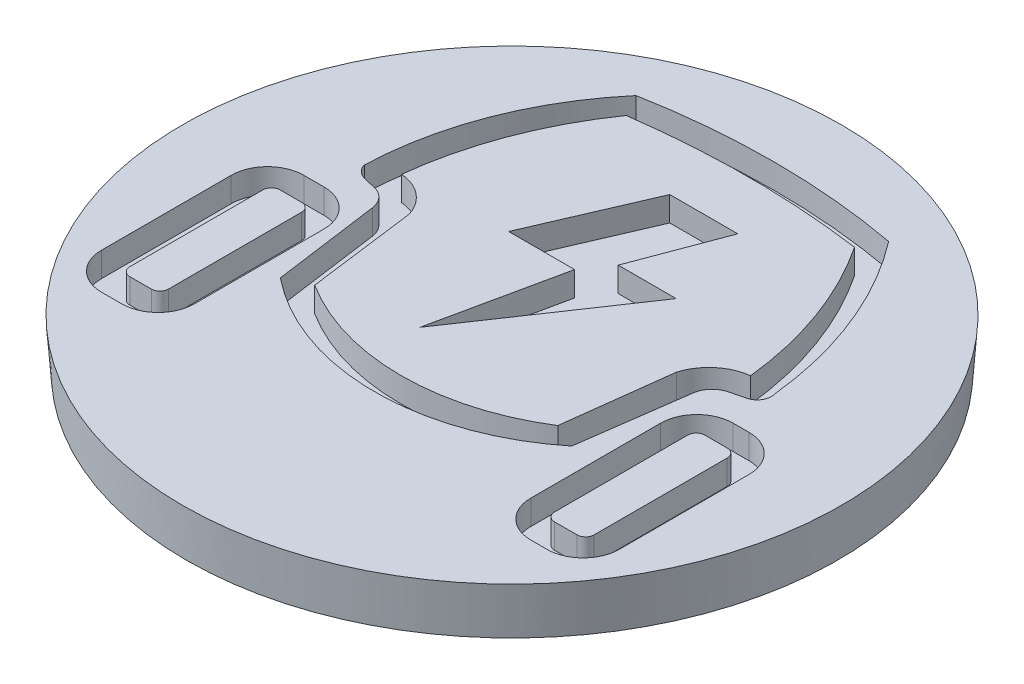
SolidWorks part; units mm, degrees
ref_plane "Alzado" through (0, 0, 0) normal (0, 0, 1) x (1, 0, 0)
ref_plane "Planta" through (0, 0, 0) normal (0, 1, 0) x (1, 0, 0)
ref_plane "Vista lateral" through (0, 0, 0) normal (1, 0, 0) x (0, 0, -1)
sketch "Croquis1" plane through (0, 0, 0) normal (0, 1, 0) x (1, 0, 0)
  circle A0 centre (0, 0) radius 26.25
extrude "Saliente-Extruir1" add sketch "Croquis1" along normal blind 4
sketch "Croquis2" plane through (0, 4, 0) normal (0, 1, 0) x (1, 0, 0)
  line L0 (48.0381, 307.552) -> (528.0381, 307.552) construction
  line L1 (-2.8746, -4.5969) -> (5.5025, 7.8219)
  line L2 (-18.2132, -0.6112) -> (-16.4707, -0.6112)
  line L3 (-18.9132, -1.3112) -> (-18.9132, -12.1089)
  line L4 (-18.2132, -12.8089) -> (-16.4707, -12.8089)
  line L5 (-15.7707, -1.3112) -> (-15.7707, -12.1089)
  line L6 (-18.2718, 1.3787) -> (-16.6299, 1.3787)
  line L7 (-21.2218, -1.5713) -> (-21.2218, -12.0991)
  line L8 (-18.2718, -15.0491) -> (-16.6299, -15.0491)
  line L9 (-13.6799, -1.5713) -> (-13.6799, -12.0991)
  line L10 (16.2668, -0.6112) -> (18.0817, -0.6112)
  line L11 (15.5668, -1.3112) -> (15.5668, -12.1089)
  line L12 (16.2668, -12.8089) -> (18.0817, -12.8089)
  line L13 (18.7817, -1.3112) -> (18.7817, -12.1089)
  line L14 (16.5776, 1.3787) -> (17.8729, 1.3787)
  line L15 (13.6276, -1.5713) -> (13.6276, -12.0991)
  line L16 (16.5776, -15.0491) -> (17.8729, -15.0491)
  line L17 (20.8229, -1.5713) -> (20.8229, -12.0991)
  line L18 (5.5025, 7.8219) -> (0.7996, 7.8219)
  line L19 (0.7996, 7.8219) -> (3.4517, 14.876)
  line L20 (3.4517, 14.876) -> (-2.0718, 14.876)
  line L21 (-2.0718, 14.876) -> (-6.0124, 5.7397)
  line L22 (-6.0124, 5.7397) -> (-0.6622, 5.7397)
  line L23 (-0.6622, 5.7397) -> (-2.8746, -4.5969)
  line L24 (9.6226, -5.9087) -> (10.6849, 2.649)
  line L25 (12.8269, 1.8801) -> (11.6311, -6.7836)
  line L26 (-12.0175, -6.7836) -> (-13.2103, 1.8867)
  line L27 (-14.3028, 3.3036) -> (-15.6415, 3.6473)
  line L28 (-11.2678, 2.9306) -> (-10.1092, -5.9087)
  line L32 (14.1731, 3.3802) -> (15.453, 3.7004)
  circle A0 centre (0, 0) radius 26.25
  arc A1 (10.6849, 2.649) -> (13.9467, 5.4173) centre (14.4042, 1.5724) cw
  arc A2 (9.6226, -5.9087) -> (-10.1092, -5.9087) centre (-0.2433, 9.7501) cw
  arc A3 (11.6311, -6.7836) -> (-12.0175, -6.7836) centre (-0.1932, 7.826) cw
  arc A4 (-11.2678, 2.9306) -> (-14.3743, 5.4173) centre (-14.6539, 1.8843) ccw
  arc A5 (-16.5412, 4.5597) -> (-10.3971, 20.4661) centre (9.2582, 3.7342) cw
  arc A6 (-14.3743, 5.4173) -> (-9.3905, 18.6676) centre (14.1573, 2.2483) cw
  arc A7 (-9.3905, 18.6676) -> (9.1313, 18.6676) centre (-0.1296, -47.7592) cw
  arc A8 (-10.3971, 20.4661) -> (10.1081, 20.4661) centre (-0.1445, -34.908) cw
  arc A9 (9.1313, 18.6676) -> (13.9467, 5.4173) centre (-15.387, 2.2571) cw
  arc A10 (10.1081, 20.4661) -> (16.1964, 5.1843) centre (-13.9789, 2.0161) cw
  arc A11 (13.6276, -12.0991) -> (16.5776, -15.0491) centre (16.5776, -12.0991) ccw
  arc A12 (17.8729, -15.0491) -> (20.8229, -12.0991) centre (17.8729, -12.0991) ccw
  arc A13 (17.8729, 1.3787) -> (20.8229, -1.5713) centre (17.8729, -1.5713) cw
  arc A14 (16.5776, 1.3787) -> (13.6276, -1.5713) centre (16.5776, -1.5713) ccw
  arc A15 (-18.2718, 1.3787) -> (-21.2218, -1.5713) centre (-18.2718, -1.5713) ccw
  arc A16 (-16.6299, 1.3787) -> (-13.6799, -1.5713) centre (-16.6299, -1.5713) cw
  arc A17 (-16.6299, -15.0491) -> (-13.6799, -12.0991) centre (-16.6299, -12.0991) ccw
  arc A18 (-21.2218, -12.0991) -> (-18.2718, -15.0491) centre (-18.2718, -12.0991) ccw
  arc A19 (-18.2132, -0.6112) -> (-18.9132, -1.3112) centre (-18.2132, -1.3112) ccw
  arc A20 (-16.4707, -0.6112) -> (-15.7707, -1.3112) centre (-16.4707, -1.3112) cw
  arc A21 (-18.9132, -12.1089) -> (-18.2132, -12.8089) centre (-18.2132, -12.1089) ccw
  arc A22 (-16.4707, -12.8089) -> (-15.7707, -12.1089) centre (-16.4707, -12.1089) ccw
  arc A23 (15.5668, -12.1089) -> (16.2668, -12.8089) centre (16.2668, -12.1089) ccw
  arc A24 (18.0817, -12.8089) -> (18.7817, -12.1089) centre (18.0817, -12.1089) ccw
  arc A25 (18.0817, -0.6112) -> (18.7817, -1.3112) centre (18.0817, -1.3112) cw
  arc A26 (16.2668, -0.6112) -> (15.5668, -1.3112) centre (16.2668, -1.3112) ccw
  arc A27 (12.8269, 1.8801) -> (14.1731, 3.3802) centre (14.61, 1.634) cw
  arc A28 (15.453, 3.7004) -> (16.1964, 5.1843) centre (15.0828, 4.8141) ccw
  arc A29 (-13.2103, 1.8867) -> (-14.3028, 3.3036) centre (-14.9935, 1.6413) ccw
  arc A30 (-16.5412, 4.5597) -> (-15.6415, 3.6473) centre (-15.3241, 4.86) ccw
  point P94 (-16.5412, 4.5597)
  dimension "D1" = 2.95
  dimension "D2" = 0.7
  dimension "D3" = 1.8
  dimension "D4" = 1.8
extrude "Cortar-Extruir2" cut sketch "Croquis2" against normal blind 2 contours L14 A14 L15 A11 L16 A12 L17 A13 A26 L10 A25 L13 A24 L12 A23 L11 | A5 A30 L27 A29 L26 A3 L25 A27 L32 A28 A10 A8 A7 A9 A1 L24 A2 L28 A4 A6 | L7 A18 L8 A17 L9 A16 L6 A15 A22 L4 A21 L3 A19 L2 A20 L5 | L18 L19 L20 L21 L22 L23 L1 region at (-17.4508, 4, -1.1979) region at (17.2253, 4, -1.1993) region at (11.7725, 4, 2.3887)
sketch "Croquis3" plane through (0, 0, 0) normal (0, -1, 0) x (1, 0, 0)
  circle A0 centre (0, 0) radius 26.25
  circle A1 centre (0, 0) radius 26.75
extrude "Saliente-Extruir2" add sketch "Croquis3" against normal blind 4
chamfer "Chaflán2" distance 4 distance2 0.3 1 edges at (0, 0, -26.75) first distance on face at (0, 4, -26.75)
